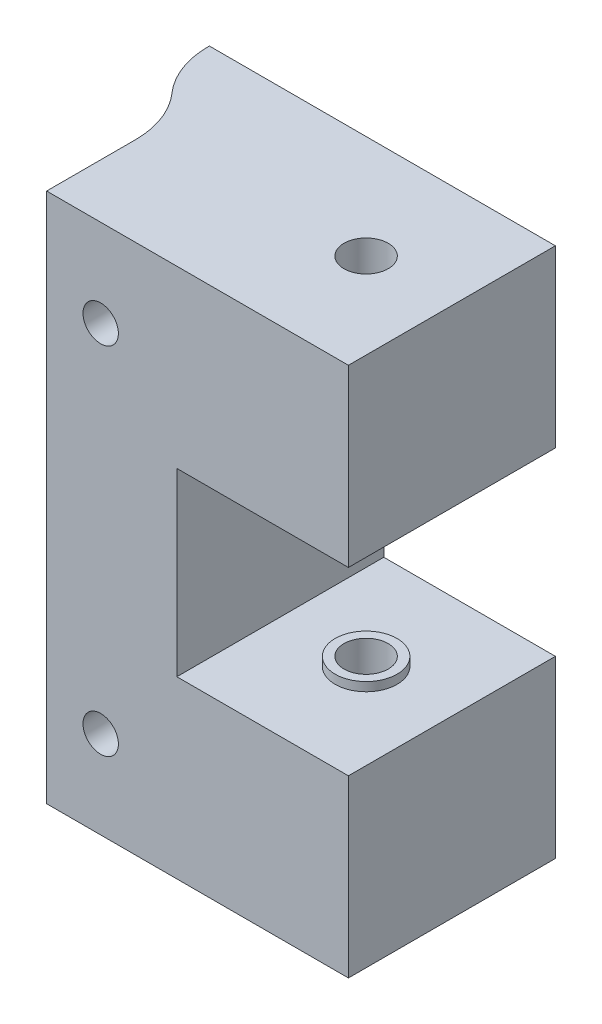
SolidWorks part; units mm, degrees
ref_plane "Front Plane" through (0, 0, 0) normal (0, 0, 1) x (1, 0, 0)
ref_plane "Top Plane" through (0, 0, 0) normal (0, 1, 0) x (1, 0, 0)
ref_plane "Right Plane" through (0, 0, 0) normal (1, 0, 0) x (0, 0, -1)
sketch "MainBlock" plane through (0, 0, 0) normal (0, 0, 1) x (1, 0, 0)
  line L0 (0, 0) -> (39.125, 0)
  line L1 (39.125, 0) -> (39.125, 19.8)
  line L2 (39.125, 19.8) -> (19.725, 19.8)
  line L3 (19.725, 19.8) -> (19.725, 40.2)
  line L4 (19.725, 40.2) -> (39.125, 40.2)
  line L5 (39.125, 40.2) -> (39.125, 60)
  line L6 (39.125, 60) -> (0, 60)
  line L7 (0, 60) -> (0, 0)
  circle A0 centre (11.1125, 50.1) radius 2
  circle A1 centre (11.1125, 9.9) radius 2
  dimension "D4" = 4
  dimension "D1" = 39.125
  dimension "D2" = 60
  dimension "D3" = 20.4
  dimension "D5" = 19.4
  dimension "D6" = 11.1125
  dimension "D7" = 9.9
  dimension "D8" = 9.9
  dimension "D9" = 19.8
  dimension "D10" = 19.8
extrude "MainBlockBoss-Extrude1" add sketch "MainBlock" along normal blind 23.4
sketch "TopHoleCut-Sketch2" plane through (0, 60, 0) normal (0, 1, 0) x (1, 0, 0)
  line L0 (39.125, 0) -> (0, 0) construction
  circle A0 centre (29.425, -11.7) radius 2.5
  dimension "D3" = 5
  dimension "D1" = 11.7
  dimension "D2" = 9.7
extrude "TopHoleCut-Extrude1" cut sketch "TopHoleCut-Sketch2" against normal blind 45
sketch "TopSpacerSketch4" plane through (0, 40.2, 0) normal (0, -1, 0) x (1, 0, 0)
  circle A0 centre (29.425, 11.7) radius 3.5
  circle A1 centre (29.425, 11.7) radius 2.5
  circle A2 centre (29.425, 11.7) radius 2.5 construction
  dimension "D1" = 7
extrude "TopSpacerBoss-Extrude2" add sketch "TopSpacerSketch4" along normal blind 1
sketch "LowerSpacerSketch5" plane through (0, 19.8, 0) normal (0, 1, 0) x (1, 0, 0)
  circle A0 centre (29.425, -11.7) radius 2.5
  circle A1 centre (29.425, -11.7) radius 2.5 construction
  circle A2 centre (29.425, -11.7) radius 3.5
  circle A3 centre (29.425, -11.7) radius 3.5 construction
extrude "LowerSpacerBoss-Extrude3" add sketch "LowerSpacerSketch5" along normal blind 1
sketch "MountHoleBoreSketch1" plane through (0, 0, 0) normal (0, 0, -1) x (-1, 0, 0)
  line L1 (-7.2375, 50.1) -> (-9.175, 53.4558)
  line L2 (-9.175, 53.4558) -> (-13.05, 53.4558)
  line L3 (-13.05, 53.4558) -> (-14.9875, 50.1)
  line L4 (-14.9875, 50.1) -> (-13.05, 46.7442)
  line L5 (-13.05, 46.7442) -> (-9.175, 46.7442)
  line L6 (-9.175, 46.7442) -> (-7.2375, 50.1)
  line L7 (-7.2375, 9.9) -> (-9.175, 13.2558)
  line L8 (-9.175, 13.2558) -> (-13.05, 13.2558)
  line L9 (-13.05, 13.2558) -> (-14.9875, 9.9)
  line L10 (-14.9875, 9.9) -> (-13.05, 6.5442)
  line L11 (-13.05, 6.5442) -> (-9.175, 6.5442)
  line L12 (-9.175, 6.5442) -> (-7.2375, 9.9)
  circle A0 centre (-11.1125, 50.1) radius 3.3558 construction
  circle A1 centre (-11.1125, 9.9) radius 3.3558 construction
  dimension "D1" = 7.75
extrude "MountHoleBoreCut-Extrude1" cut sketch "MountHoleBoreSketch1" against normal blind 2
sketch "PushPinHoleSketch1" plane through (0, 0, 0) normal (0, -1, 0) x (1, 0, 0)
  circle A0 centre (29.425, 11.7) radius 1
  circle A1 centre (29.425, 11.7) radius 2.5 construction
  dimension "D1" = 2
extrude "PushPinHoleCut-Extrude1" cut sketch "PushPinHoleSketch1" against normal through all
sketch "ScrewCollisionSketch1" plane through (0, 0, 0) normal (-1, 0, 0) x (0, 0, 1)
  line L0 (23.4, 60) -> (23.4, 0) construction
  line L1 (23.4, 60) -> (4.68, 60)
  line L2 (23.4, 60) -> (23.4, 0)
  line L3 (23.4, 0) -> (4.68, 0)
  line L4 (4.68, 60) -> (4.68, 0)
  line L5 (23.4, 0) -> (0, 0) construction
  line L6 (23.4, 60) -> (0, 60) construction
  dimension "D1" = 18.72
extrude "Cut-Extrude1" cut sketch "ScrewCollisionSketch1" against normal blind 5
fillet "Fillet1" radius 10 1 edges at (5, 30, 4.68)
fillet "Fillet2" radius 10 1 edges at (0, 30, 4.68)
sketch "MidRailInsetSketch1" plane through (0, 0, 0) normal (0, 0, -1) x (-1, 0, 0)
  line L0 (0, 60) -> (0, 0) construction
  line L1 (0, 45.1) -> (-3.18, 45.1)
  line L2 (0, 45.1) -> (0, 0)
  line L3 (0, 0) -> (-3.18, 0)
  line L4 (-3.18, 45.1) -> (-3.18, 0)
  line L6 (0, 0) -> (-39.125, 0) construction
  line L7 (-39.125, 60) -> (0, 60) construction
  dimension "D1" = 3.18
  dimension "D2" = 14.9
extrude "MidRailInsetCut-Extrude2" cut sketch "MidRailInsetSketch1" against normal through all
equation "\"BeltTensionerWidth\"= \"MidRailToAlignWithGantryBlock\" + \"BeltTensionerInnerWidth\" / 2 + \"RailThickness\""
equation "\"BeltTensionerHeight\"= 60mm"
equation "\"BeltTensionerDepth\"= \"BeltTensionerBackWallThickness\" + \"BeltTensionerInnerDepth\"'Equals 23.4"
equation "\"BeltTensionerInnerWidth\"= \"20TGT2PulleyDiameter\" + \"BeltTensionerSpaceBetweenPulleyAndWall\""
equation "\"BeltTensionerInnerHeight\"= \"20TGT2PulleyWidth\" * 2 + \"1mmSpacer\" * 3"
equation "\"BeltTensionerBackWallThickness\"= 4mm"
equation "\"BeltTensionerInnerDepth\"= \"20TGT2PulleyDiameter\" + \"BeltTensionerSpaceBetweenPulleyAndWall\""
equation "\"RailThickness\"= .125in'Spec"
equation "\"HoleOffsetFromEdge\"= \"RailThickness\" * 2.5"
equation "\"LinearGBWithRailDepth\"= 12.75mm'Spec"
equation "\"GABDistanceFromBackToFirstPulley\"= 13.5mm"
equation "\"MidRailToAlignWithGantryBlock\"= \"LinearGBWithRailDepth\" + \"GABDistanceFromBackToFirstPulley\"'All outside cogs must align"
equation "\"20TGT2PulleyDiameter\"= 17.9mm'Spec"
equation "\"BeltTensionerSpaceBetweenPulleyAndWall\"= 1.5mm"
equation "\"BeltTensionerMountingHoleDiameter\"= 4.0mm"
equation "\"BeltTensionerMountingHoleOffsetFromEdge\"= \"HoleOffsetFromEdge\""
equation "\"20TGT2PulleyWidth\"= 8.7mm'The STL of the Pulley in the diagram is a bit larger"
equation "\"1mmSpacer\"= 1mm"
equation "\"SteelShaft5mmHoleDiameter\"= 5mm"
equation "\"BeltTensionerMountingHoleOuterBoreDepth\"= 2mm"
equation "\"BeltTensionerMountingHoleOuterBoreDiameter\"= 7.75mm"
equation "\"7mmx1mmSpacerDiameter\"= 7mm"
equation "\"7mmx1mmSpacerHeight\"= 1mm"
equation "\"D1@MainBlock\" = \"BeltTensionerWidth\""
equation "\"D4@MainBlock\" = \"BeltTensionerMountingHoleDiameter\""
equation "\"D5@MainBlock\" = \"BeltTensionerInnerWidth\""
equation "\"D6@MainBlock\"=\"BeltTensionerMountingHoleOffsetFromEdge\" + \"RailThickness\""
equation "\"D7@MainBlock\"=\"BeltTensionerMountingHoleOffstFromTopOrBottom\""
equation "\"D8@MainBlock\"=\"BeltTensionerMountingHoleOffstFromTopOrBottom\""
equation "\"D1@MainBlockBoss-Extrude1\" = \"BeltTensionerDepth\""
equation "\"D1@TopHoleCut-Sketch2\" = \"BeltTensionerDepth\" / 2"
equation "\"D3@TopHoleCut-Sketch2\" = \"SteelShaft5mmHoleDiameter\""
equation "\"D1@TopSpacerSketch4\" = \"7mmx1mmSpacerDiameter\""
equation "\"D1@TopSpacerBoss-Extrude2\" = \"7mmx1mmSpacerHeight\""
equation "\"D1@LowerSpacerBoss-Extrude3\" = \"7mmx1mmSpacerHeight\""
equation "\"D1@MountHoleBoreSketch1\" = \"BeltTensionerMountingHoleOuterBoreDiameter\""
equation "\"D1@MountHoleBoreCut-Extrude1\" = \"BeltTensionerMountingHoleOuterBoreDepth\""
equation "\"SteelPinPushHoleDiameter\"= 2mm"
equation "\"D1@PushPinHoleSketch1\" = \"SteelPinPushHoleDiameter\""
equation "\"D2@TopHoleCut-Sketch2\"=\"BeltTensionerWidth\" - \"MidRailToAlignWithGantryBlock\" - \"RailThickness\""
equation "\"BeltTensionerMountingHoleOffstFromTopOrBottom\"= ( \"BeltTensionerHeight\" - \"BeltTensionerInnerHeight\" ) / 4"
equation "\"BeltTensionerSteelShaftHoleDepthFromTop\"= ( \"SteelShaftLength\" - \"BeltTensionerInnerHeight\" ) / 2 + ( \"BeltTensionerHeight\" - \"BeltTensionerInnerHeight\" ) / 2 + \"BeltTensionerInnerHeight\"'Equals 45"
equation "\"SteelShaftLength\"= 30mm"
equation "\"D1@TopHoleCut-Extrude1\"=\"BeltTensionerSteelShaftHoleDepthFromTop\""
equation "\"D1@ScrewCollisionSketch1\" = \"BeltTensionerDepth\" * .8"
equation "\"MidSideRailVerticalOffset\"= \"LinearRailWidth\" + 3mm'Allows space for RodStabilizer to attach to bottom of MidSideRail"
equation "\"LinearRailWidth\"= 12mm'Spec"
equation "\"D2@MidRailInsetSketch1\"=\"DistanceAboveMidSideRailToTopOfBeltTensioner\""
equation "\"DistanceAboveMidSideRailToTopOfBeltTensioner\"= \"VS ToTopOfBeltTensionerAlignedWithYAxisGantryBlockUpperPulley\" - \"V8 ToTopOfMidSideRail\"'Equals 14.9"
equation "\"DistanceFromBeltTensionerTopPulleyToBeltTensionerTop\"= \"7mmx1mmSpacerHeight\" + \"BeltTensionerTopHeight\"'Equals 20.8"
equation "\"BeltTensionerTopHeight\"= ( \"BeltTensionerHeight\" - \"BeltTensionerInnerHeight\" ) / 2'Equals 19.8"
equation "\"GABUpperHeight\"= 4mm"
equation "\"D3@MainBlock\"=\"BeltTensionerInnerHeight\""
equation "\"D9@MainBlock\"=\"BeltTensionerTopHeight\""
equation "\"LegHeight\"= 70mm'Space needed for PSU/Stepper/Electronics"
equation "\"V1 BottomOfLowerRail\"= \"LegHeight\""
equation "\"LowerEnclosureThickness\"= 5mm"
equation "\"StepperShaftLength\"= 24mm'Pulley will be attached to the end"
equation "\"ZAxisLeadScrewLength\"= 200mm"
equation "\"LM8UUHeight\"= 24mm'Spec"
equation "\"V2 ToBedAtTopOfZAxis\"= \"V1 BottomOfLowerRail\" - \"LowerEnclosureThickness\" + \"StepperShaftLength\" + \"ZAxisLeadScrewLength\" - \"LM8UUHeight\" / 2'Equals 277"
equation "\"BedToBuildPlateStandoffLength\"= 15mm"
equation "\"BuildPlateHeight\"= 8mm'Spec"
equation "\"V4 ToTopOfBuildPlate/HotEndTip\"= \"V2 ToBedAtTopOfZAxis\" + \"BedToBuildPlateStandoffLength\" + \"BuildPlateHeight\""
equation "\"HotEndToTopOfXAxisGB\"= 71.68487mm'Equals 71.68487. Measured after installed onto X-Axis linear rail guide block"
equation "\"LinearGBWidth\"= 27mm'Spec"
equation "\"TopOfGBToBottomOfLinearRail\"= \"LinearGBWidth\" / 2 + \"LinearRailWidth\" / 2'Equals 19.5"
equation "\"V5 ToBottomOfXAxisLinearRail\"= \"V4 ToTopOfBuildPlate/HotEndTip\" + \"HotEndToTopOfXAxisGB\" - \"TopOfGBToBottomOfLinearRail\"'Equals 352.18487"
equation "\"GABMidWallHeight\"= 28mm'Must equal 28 or changes alignment"
equation "\"GABLowerHeight\"= 4mm"
equation "\"GABHeight\"= \"GABLowerHeight\" + \"GABMidWallHeight\" + \"GABUpperHeight\""
equation "\"V6 ToMiddleOfYAxisGantryBlock\"= \"V5 ToBottomOfXAxisLinearRail\" - \"GABHeight\" / 2'Equals 334.18487"
equation "\"V8 ToTopOfMidSideRail\"= \"V6 ToMiddleOfYAxisGantryBlock\" + \"MidSideRailVerticalOffset\"'Equals 349.18487"
equation "\"VS ToTopOfBeltTensionerAlignedWithYAxisGantryBlockUpperPulley\"= \"V5 ToBottomOfXAxisLinearRail\" - \"DistanceFromXAxisLinearRailBottomAndTopOfGantryPulley\" + \"DistanceFromBeltTensionerTopPulleyToBeltTensionerTop\"'Equals 364.08487"
equation "\"GABRiserBossOffset\"= 0.4mm'Aligns Pulleys inside edges to be 2.5mm (.5mm apart top to bottom)"
equation "\"GABMidShortRiserHeight\"= \"GABMidWallHeight\" / 2 - \"20TGT2PulleyWidth\"'Equals 5.3"
equation "\"DistanceFromXAxisLinearRailBottomAndTopOfGantryPulley\"= \"GABUpperHeight\" + \"GABMidShortRiserHeight\" - \"GABRiserBossOffset\"'Equals 8.9"
